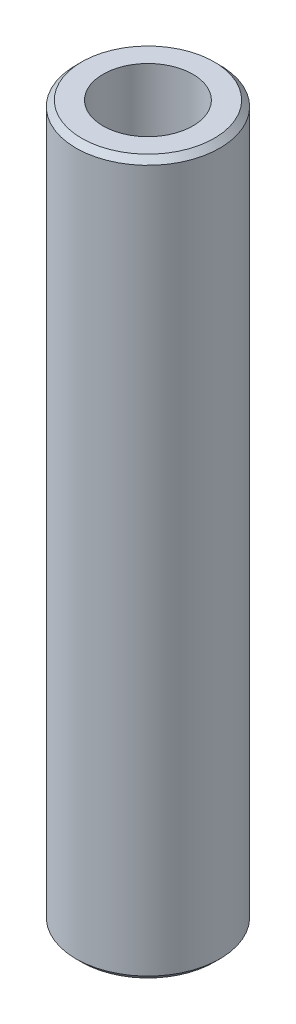
SolidWorks part; units mm, degrees
material "Alloy Steel"
ref_plane "Front Plane" through (0, 0, 0) normal (0, 0, 1) x (1, 0, 0)
ref_plane "Top Plane" through (0, 0, 0) normal (0, 1, 0) x (1, 0, 0)
ref_plane "Right Plane" through (0, 0, 0) normal (1, 0, 0) x (0, 0, -1)
sketch "Sketch1" plane through (0, 0, 0) normal (0, 1, 0) x (1, 0, 0)
  circle A0 centre (0, 0) radius 7.9248
  circle A1 centre (0, 0) radius 12.7
  dimension "D1" = 25.4
  dimension "D2" = 15.8496
extrude "Boss-Extrude1" add sketch "Sketch1" along normal mid plane 126
chamfer "Chamfer1" distance 1 angle 45 2 edges at (0, -63, 12.7) (0, 63, 12.7)
